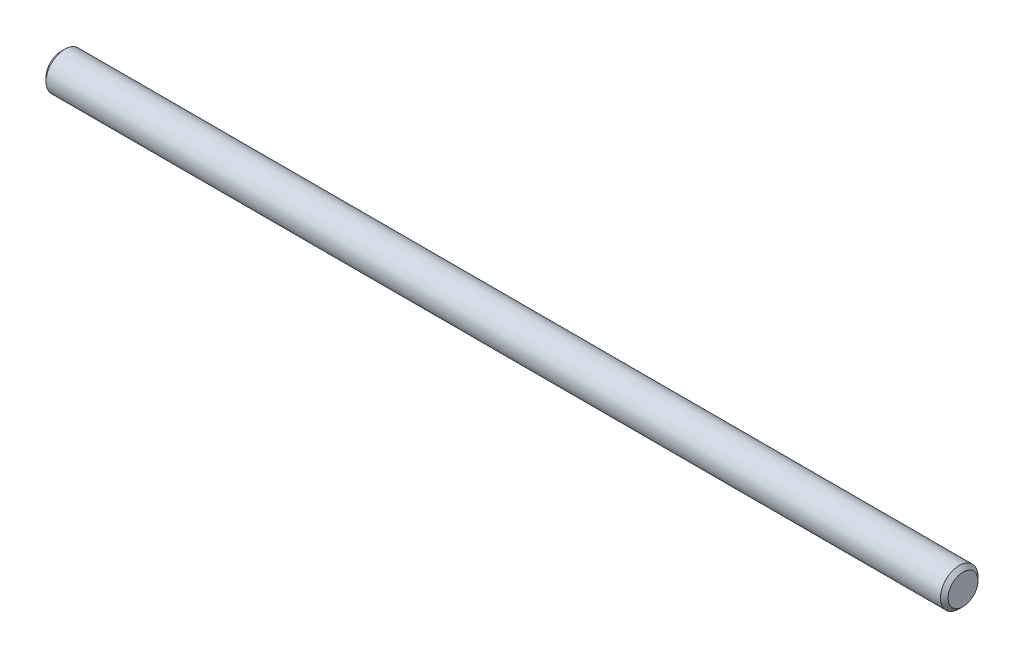
SolidWorks part; units mm, degrees
ref_plane "Front Plane" through (0, 0, 0) normal (0, 0, 1) x (1, 0, 0)
ref_plane "Top Plane" through (0, 0, 0) normal (0, 1, 0) x (1, 0, 0)
ref_plane "Right Plane" through (0, 0, 0) normal (1, 0, 0) x (0, 0, -1)
sketch "Sketch1" plane through (0, 0, 0) normal (1, 0, 0) x (0, 0, -1)
  circle A0 centre (0, 0) radius 4
  dimension "D1" = 8
extrude "Boss-Extrude1" add sketch "Sketch1" along normal mid plane 192
cosmetic thread "Cosmetic Thread1" parameters "D1"=10, "D2"=6.891
cosmetic thread "Cosmetic Thread2" parameters "D1"=10, "D2"=6.891
chamfer "Chamfer1" distance 0.81 angle 45 2 edges at (96, 0, -4) (-96, 0, -4)
